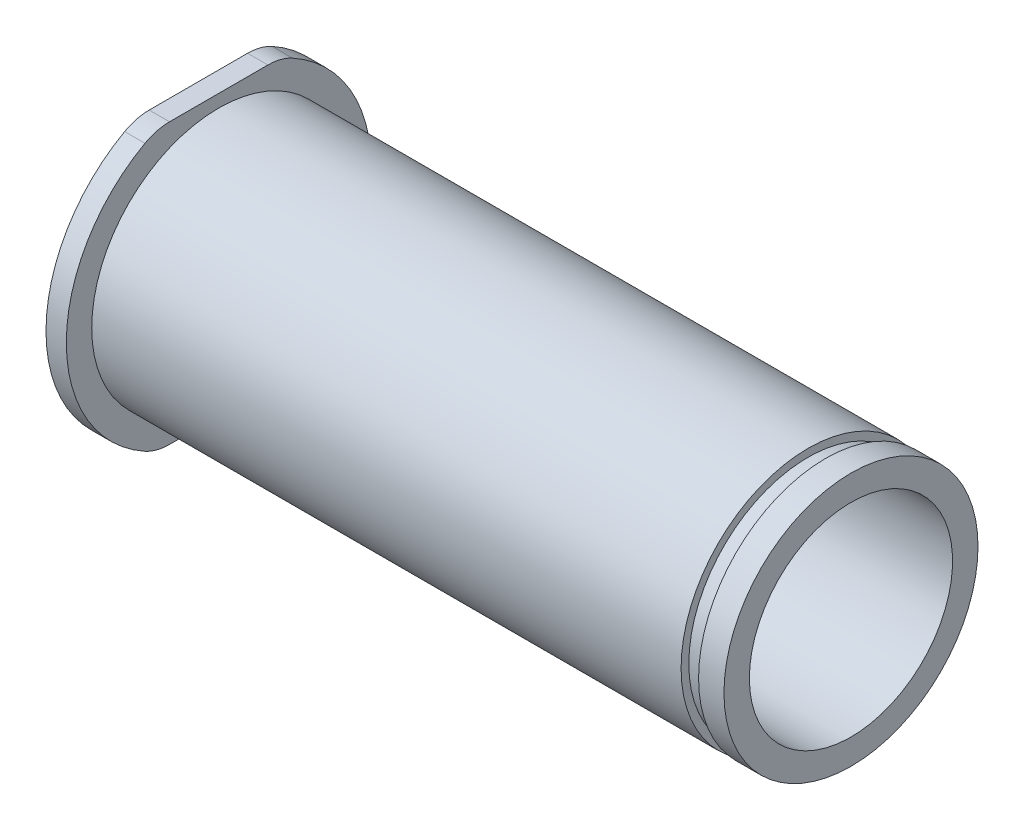
SolidWorks part; units mm, degrees
material "6061 Alloy"
ref_plane "Front Plane" through (0, 0, 0) normal (0, 0, 1) x (1, 0, 0)
ref_plane "Top Plane" through (0, 0, 0) normal (0, 1, 0) x (1, 0, 0)
ref_plane "Right Plane" through (0, 0, 0) normal (1, 0, 0) x (0, 0, -1)
sketch "Sketch1" plane through (0, 0, 0) normal (0, 0, 1) x (1, 0, 0)
  line L0 (0, 0) -> (81.5594, 0) construction
  line L1 (0, 12.7) -> (81.5594, 12.7)
  line L2 (81.5594, 12.7) -> (81.5594, 15.875)
  line L3 (81.5594, 15.875) -> (78.3844, 15.875)
  line L4 (78.3844, 15.875) -> (78.3844, 14.9098)
  line L5 (78.3844, 14.9098) -> (76.2, 14.9098)
  line L6 (76.2, 14.9098) -> (76.2, 15.875)
  line L7 (76.2, 15.875) -> (2.54, 15.875)
  line L8 (2.54, 15.875) -> (2.54, 19.05)
  line L9 (2.54, 19.05) -> (0, 19.05)
  line L10 (0, 19.05) -> (0, 12.7)
  dimension "D1" = 76.2
  dimension "D2" = 2.54
  dimension "D3" = 38.1
  dimension "D4" = 31.75
  dimension "D5" = 2.1844
  dimension "D6" = 29.8196
  dimension "D7" = 3.175
  dimension "D8" = 25.4
revolve "Revolve1" add sketch "Sketch1" angle 360 about L0
sketch "Sketch2" plane through (0, 0, 0) normal (-1, 0, 0) x (0, 0, 1)
  line L0 (-7.6134, 17.4625) -> (7.6134, 17.4625)
  line L1 (7.6134, 17.4625) -> (7.6134, 19.05)
  line L2 (7.6134, 19.05) -> (-7.6134, 19.05)
  line L3 (-7.6134, 19.05) -> (-7.6134, 17.4625)
  line L4 (-7.6134, -17.4625) -> (7.6134, -17.4625)
  line L5 (7.6134, -17.4625) -> (7.6134, -19.05)
  line L6 (7.6134, -19.05) -> (-7.6134, -19.05)
  line L7 (-7.6134, -19.05) -> (-7.6134, -17.4625)
  line L8 (0, 17.4625) -> (0, -17.4625) construction
  circle A0 centre (0, 0) radius 19.05 construction
  dimension "D1" = 34.925
extrude "Cut-Extrude1" cut sketch "Sketch2" against normal up to next
fillet "Fillet1" radius 6.35 4 edges at (1.27, -17.4625, -7.6134) (1.27, -17.4625, 7.6134) (1.27, 17.4625, -7.6134) (1.27, 17.4625, 7.6134)
